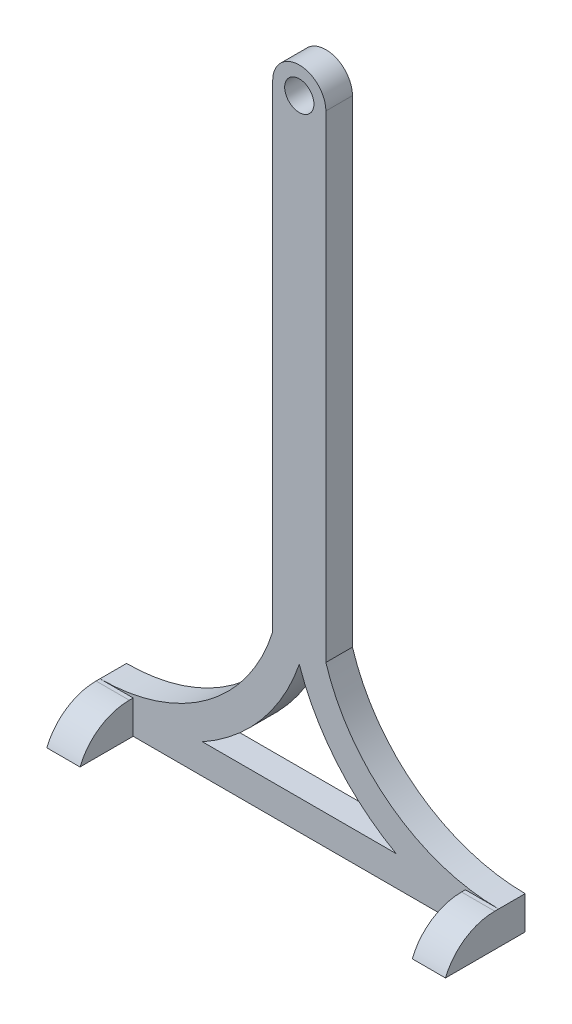
SolidWorks part; units mm, degrees
ref_plane "Front Plane" through (0, 0, 0) normal (0, 0, 1) x (1, 0, 0)
ref_plane "Top Plane" through (0, 0, 0) normal (0, 1, 0) x (1, 0, 0)
ref_plane "Right Plane" through (0, 0, 0) normal (1, 0, 0) x (0, 0, -1)
sketch "Sketch1" plane through (0, 0, 0) normal (0, 0, 1) x (1, 0, 0)
  line L5 (0, 100) -> (0, 0) construction
  line L6 (-30, 0) -> (30, 0)
  line L9 (30, 0) -> (30, 5)
  line L17 (4, 96) -> (4, 24.1245)
  line L18 (-4, 96) -> (-4, 24.1245)
  line L19 (-30, 0) -> (-30, 5)
  line L21 (14.5764, 4.5) -> (14.5764, 4.5)
  line L22 (-14.5764, 4.5) -> (14.5764, 4.5)
  line L23 (-14.5764, 4.5) -> (-14.5764, 4.5)
  line L25 (0.5, 96) -> (0.5, 23.4656) construction
  line L26 (-0.5, 96) -> (-0.5, 23.4656) construction
  circle A3 centre (0, 96) radius 2.2
  arc A5 (30, 5) -> (4, 24.1245) centre (30, 32.2359) cw
  arc A7 (-30, 5) -> (-4, 24.1245) centre (-30, 32.2359) ccw
  arc A8 (14.5764, 4.5) -> (0, 21.8837) centre (30, 32.2359) cw
  arc A9 (4, 96) -> (-4, 96) centre (0, 96) ccw
  arc A10 (-14.5764, 4.5) -> (0, 21.8837) centre (-30, 32.2359) ccw
  arc A11 (-14.5764, 4.5) -> (0.5, 23.4656) centre (-30, 32.2359) ccw construction
  arc A12 (14.5764, 4.5) -> (-0.5, 23.4656) centre (30, 32.2359) cw construction
  point P0 (0, 0)
  point P15 (0, 0)
  point P18 (0, 0)
  dimension "D4" = 30
  dimension "D5" = 0
  dimension "D6" = 4
  dimension "D7" = 4.4
  dimension "D3" = 27.2359
  dimension "D1" = 100
  dimension "D2" = 5
  dimension "D8" = 4.5
extrude "Boss-Extrude1" add sketch "Sketch1" along normal blind 4
sketch "Sketch2" plane through (0, 0, 4) normal (0, 0, 1) x (1, 0, 0)
  line L5 (30, 0) -> (25, 0)
  line L6 (30, 0) -> (30, 5)
  line L7 (30, 5) -> (25, 5)
  line L8 (25, 0) -> (25, 5)
  line L9 (-30, 0) -> (-25, 0)
  line L10 (-30, 0) -> (-30, 5)
  line L11 (-30, 5) -> (-25, 5)
  line L12 (-25, 0) -> (-25, 5)
  dimension "D1" = 5
  dimension "D2" = 5
  dimension "D3" = 5
  dimension "D4" = 5
extrude "Boss-Extrude2" add sketch "Sketch2" along normal blind 8
fillet "Fillet1" radius 8 2 edges at (27.5, 5, 12) (-27.5, 5, 12)
